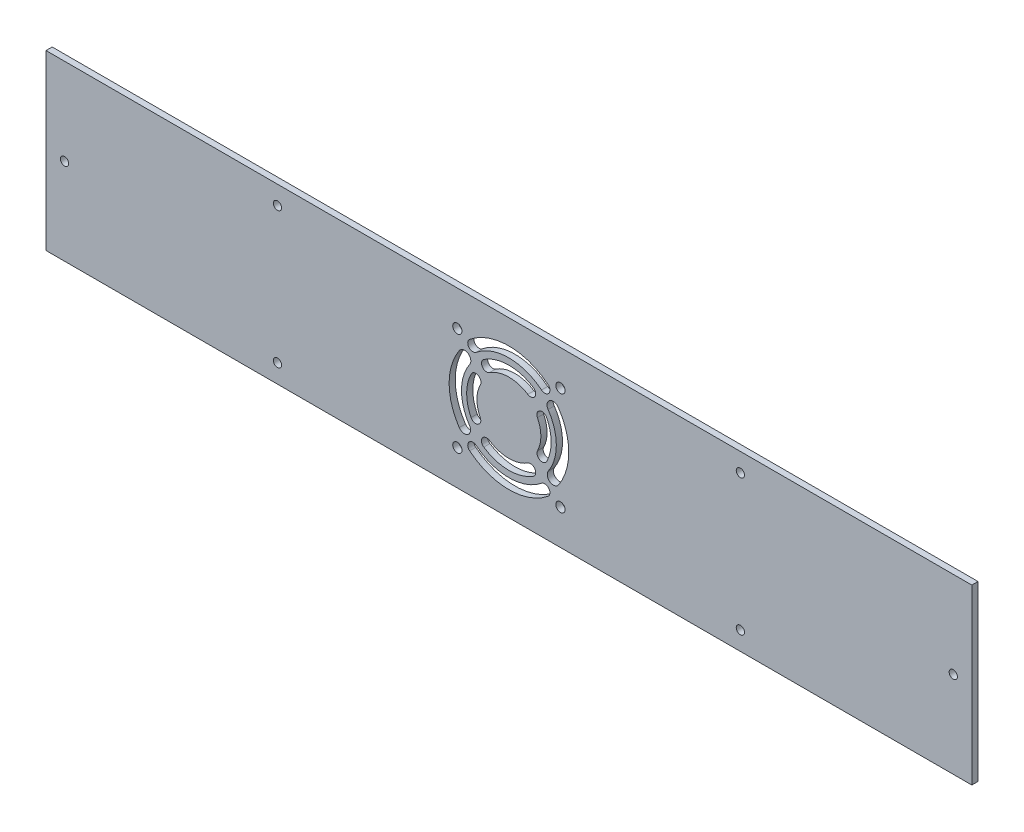
SolidWorks part; units mm, degrees
ref_plane "Piano frontale" through (0, 0, 0) normal (0, 0, 1) x (1, 0, 0)
ref_plane "Piano superiore" through (0, 0, 0) normal (0, 1, 0) x (1, 0, 0)
ref_plane "Piano destro" through (0, 0, 0) normal (1, 0, 0) x (0, 0, -1)
sketch "Schizzo1" plane through (0, 0, 0) normal (0, 0, 1) x (1, 0, 0)
  line L0 (0, 0) -> (0, 84)
  line L1 (0, 84) -> (449, 84)
  line L2 (449, 84) -> (449, 0)
  line L3 (449, 0) -> (0, 0)
  line L4 (0, 42) -> (449, 42) construction
  line L5 (224.5, 42) -> (224.5, 123.488) construction
  line L6 (224.5, 84) -> (0, 0) construction
  line L7 (112.25, 42) -> (112.25, 84) construction
  circle A0 centre (9, 42) radius 2
  circle A3 centre (440, 42) radius 2
  circle A5 centre (199.5, 67) radius 2.25
  circle A6 centre (199.5, 17) radius 2.25
  circle A7 centre (249.5, 17) radius 2.25
  circle A8 centre (249.5, 67) radius 2.25
  circle A9 centre (112.25, 75) radius 2
  circle A10 centre (336.75, 75) radius 2
  circle A11 centre (336.75, 9) radius 2
  circle A12 centre (112.25, 9) radius 2
  point P46 (173, 42)
  point P94 (173, 42)
  dimension "D3" = 9
  dimension "D6" = 4
  dimension "D7" = 4
  dimension "D1" = 84
  dimension "D2" = 449
  dimension "D8" = 9
  dimension "D13" = 50
  dimension "D14" = 50
extrude "Estrusione-Estrusione1" add sketch "Schizzo1" along normal blind 3
sketch "Schizzo2" plane through (0, 0, 3) normal (0, 0, 1) x (1, 0, 0)
  line L0 (199.5, 67) -> (249.5, 17) construction
  line L1 (249.5, 17) -> (249.5, 67) construction
  line L2 (249.5, 67) -> (199.5, 17) construction
  line L3 (224.5, 42) -> (224.5, 69.5265) construction
  line L4 (224.5, 42) -> (212.3167, 42) construction
  arc A0 (208.446, 50.141) -> (208.3716, 34.0074) centre (224.5, 42) ccw construction
  arc A1 (206.2163, 51.2717) -> (206.1315, 32.8974) centre (224.5, 42) ccw
  arc A2 (210.6757, 49.0103) -> (210.6116, 35.1175) centre (224.5, 42) ccw
  arc A3 (210.6757, 49.0103) -> (206.2163, 51.2717) centre (208.446, 50.141) ccw
  arc A4 (206.1315, 32.8974) -> (210.6116, 35.1175) centre (208.3716, 34.0074) ccw
  arc A5 (202.9084, 27.515) -> (203.0212, 56.6517) centre (224.5, 42) cw construction
  arc A6 (200.5429, 58.3423) -> (200.4171, 25.8437) centre (224.5, 42) ccw
  arc A7 (205.4995, 54.9611) -> (205.3997, 29.1864) centre (224.5, 42) ccw
  arc A8 (205.4995, 54.9611) -> (200.5429, 58.3423) centre (203.0212, 56.6517) ccw
  arc A9 (200.4171, 25.8437) -> (205.3997, 29.1864) centre (202.9084, 27.515) ccw
  arc A10 (240.554, 50.141) -> (240.6284, 34.0074) centre (224.5, 42) cw construction
  arc A11 (242.7837, 51.2717) -> (242.8685, 32.8974) centre (224.5, 42) cw
  arc A12 (238.3243, 49.0103) -> (238.3884, 35.1175) centre (224.5, 42) cw
  arc A13 (238.3243, 49.0103) -> (242.7837, 51.2717) centre (240.554, 50.141) cw
  arc A14 (242.8685, 32.8974) -> (238.3884, 35.1175) centre (240.6284, 34.0074) cw
  arc A15 (246.0916, 27.515) -> (245.9788, 56.6517) centre (224.5, 42) ccw construction
  arc A16 (248.4571, 58.3423) -> (248.5829, 25.8437) centre (224.5, 42) cw
  arc A17 (243.5005, 54.9611) -> (243.6003, 29.1864) centre (224.5, 42) cw
  arc A18 (243.5005, 54.9611) -> (248.4571, 58.3423) centre (245.9788, 56.6517) cw
  arc A19 (248.5829, 25.8437) -> (243.6003, 29.1864) centre (246.0916, 27.515) cw
  arc A20 (235.0095, 58.5335) -> (213.6955, 58.3423) centre (224.5, 42) ccw construction
  arc A21 (236.3506, 60.6434) -> (212.3167, 60.4277) centre (224.5, 42) ccw
  arc A22 (233.6684, 56.4237) -> (215.0742, 56.2568) centre (224.5, 42) ccw
  arc A23 (233.6684, 56.4237) -> (236.3506, 60.6434) centre (235.0095, 58.5335) ccw
  arc A24 (212.3167, 60.4277) -> (215.0742, 56.2568) centre (213.6955, 58.3423) ccw
  arc A25 (241.8996, 63.5299) -> (207.0329, 63.4752) centre (224.5, 42) ccw construction
  arc A26 (243.471, 65.4744) -> (205.4554, 65.4147) centre (224.5, 42) ccw
  arc A27 (240.3282, 61.5855) -> (208.6104, 61.5358) centre (224.5, 42) ccw
  arc A28 (240.3282, 61.5855) -> (243.471, 65.4744) centre (241.8996, 63.5299) ccw
  arc A29 (205.4554, 65.4147) -> (208.6104, 61.5358) centre (207.0329, 63.4752) ccw
  arc A30 (241.8996, 20.4701) -> (207.0329, 20.5248) centre (224.5, 42) cw construction
  arc A31 (243.471, 18.5256) -> (205.4554, 18.5853) centre (224.5, 42) cw
  arc A32 (240.3282, 22.4145) -> (208.6104, 22.4642) centre (224.5, 42) cw
  arc A33 (240.3282, 22.4145) -> (243.471, 18.5256) centre (241.8996, 20.4701) cw
  arc A34 (205.4554, 18.5853) -> (208.6104, 22.4642) centre (207.0329, 20.5248) cw
  arc A35 (235.0095, 25.4665) -> (213.6955, 25.6577) centre (224.5, 42) cw construction
  arc A36 (236.3506, 23.3566) -> (212.3167, 23.5723) centre (224.5, 42) cw
  arc A37 (233.6684, 27.5763) -> (215.0742, 27.7432) centre (224.5, 42) cw
  arc A38 (233.6684, 27.5763) -> (236.3506, 23.3566) centre (235.0095, 25.4665) cw
  arc A39 (212.3167, 23.5723) -> (215.0742, 27.7432) centre (213.6955, 25.6577) cw
  point P7 (206.5, 42.083)
  point P12 (198.5, 42.1006)
  point P24 (242.5, 42.083)
  point P31 (250.5, 42.1006)
  point P39 (224.3242, 61.5902)
  point P47 (224.4566, 69.6818)
  point P56 (224.4566, 14.3182)
  point P63 (224.3242, 22.4098)
  dimension "D1" = 5
  dimension "D2" = 6
  dimension "D5" = 5
  dimension "D6" = 5
  dimension "D3" = 8
  dimension "D4" = 26
extrude "Taglio-Estrusione1" cut sketch "Schizzo2" against normal blind 10
